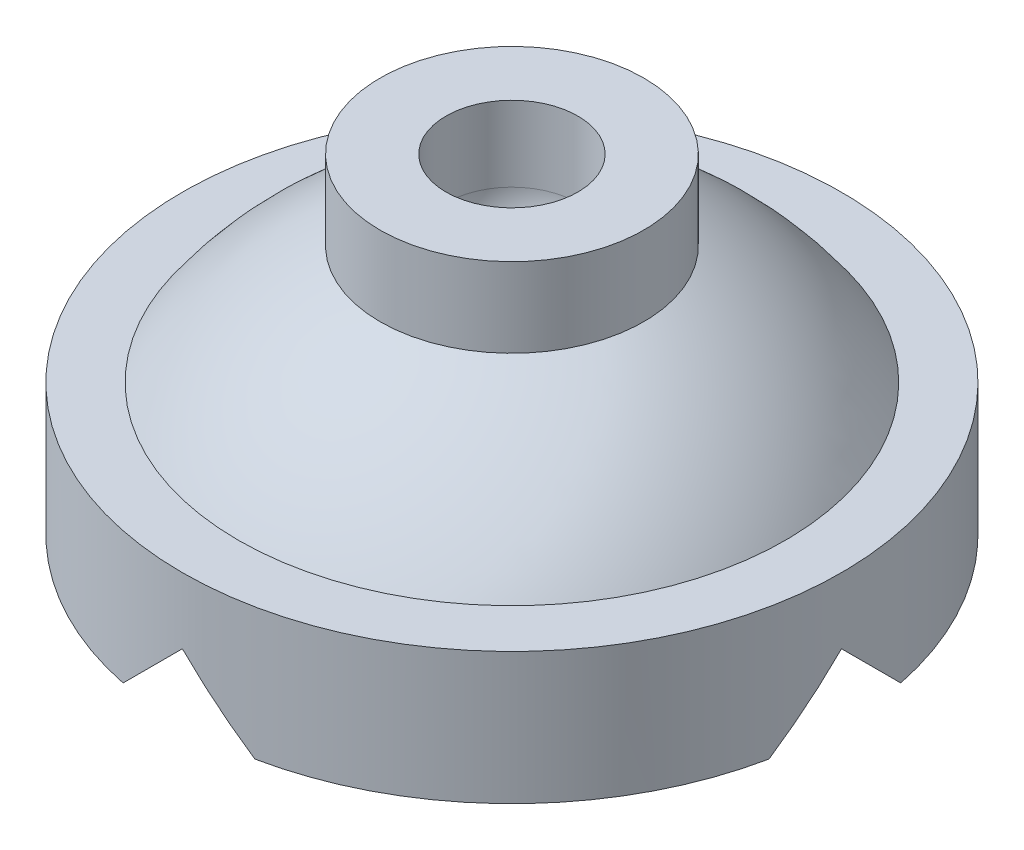
SolidWorks part; units mm, degrees
ref_plane "Спереди" through (0, 0, 0) normal (0, 0, 1) x (1, 0, 0)
ref_plane "Сверху" through (0, 0, 0) normal (0, 1, 0) x (1, 0, 0)
ref_plane "Справа" through (0, 0, 0) normal (1, 0, 0) x (0, 0, -1)
sketch "Эскиз1" plane through (0, 0, 0) normal (1, 0, 0) x (0, 0, -1)
  line L0 (0, 30.0681) -> (0, -15.5446) construction
  line L1 (0, 0) -> (25, 0)
  line L2 (25, 0) -> (25, 10)
  line L3 (25, 10) -> (20.7483, 10)
  line L4 (10, 18.9813) -> (10, 25)
  line L5 (10, 25) -> (5, 25)
  line L6 (0, 14.1831) -> (0, 0)
  line L7 (5, 25) -> (5, 19.2909)
  arc A0 (20.7483, 10) -> (10, 18.9813) centre (-0.9908, -5.0941) ccw
  arc A1 (0, 14.1831) -> (5, 19.2909) centre (-0.0539, 19.237) ccw
  point P9 (5, 19.4053)
revolve "Повернуть1" add sketch "Эскиз1" angle 360 about L0
sketch "Эскиз2" plane through (0, 0, 0) normal (0, 0, 1) x (1, 0, 0)
  line L0 (-5, 0) -> (5, 0)
  line L1 (5, 0) -> (0, 5)
  line L2 (0, 5) -> (-5, 0)
  point P3 (4.7604, 0)
  point P5 (0, 0)
  point P6 (0, 0)
extrude "Вырез-Вытянуть1" cut sketch "Эскиз2" against normal mid plane 60
sketch "Эскиз3" plane through (0, 0, 0) normal (1, 0, 0) x (0, 0, -1)
  line L0 (-5, 0) -> (0, 5)
  line L1 (-24.4949, 0) -> (24.4949, 0) construction
  line L2 (0, 5) -> (5, 0)
  line L3 (5, 0) -> (-5, 0)
  point P4 (0, 0)
  point P6 (0, 0)
  point P7 (0, 0)
extrude "Вырез-Вытянуть2" cut sketch "Эскиз3" against normal through all both and the other way through all
